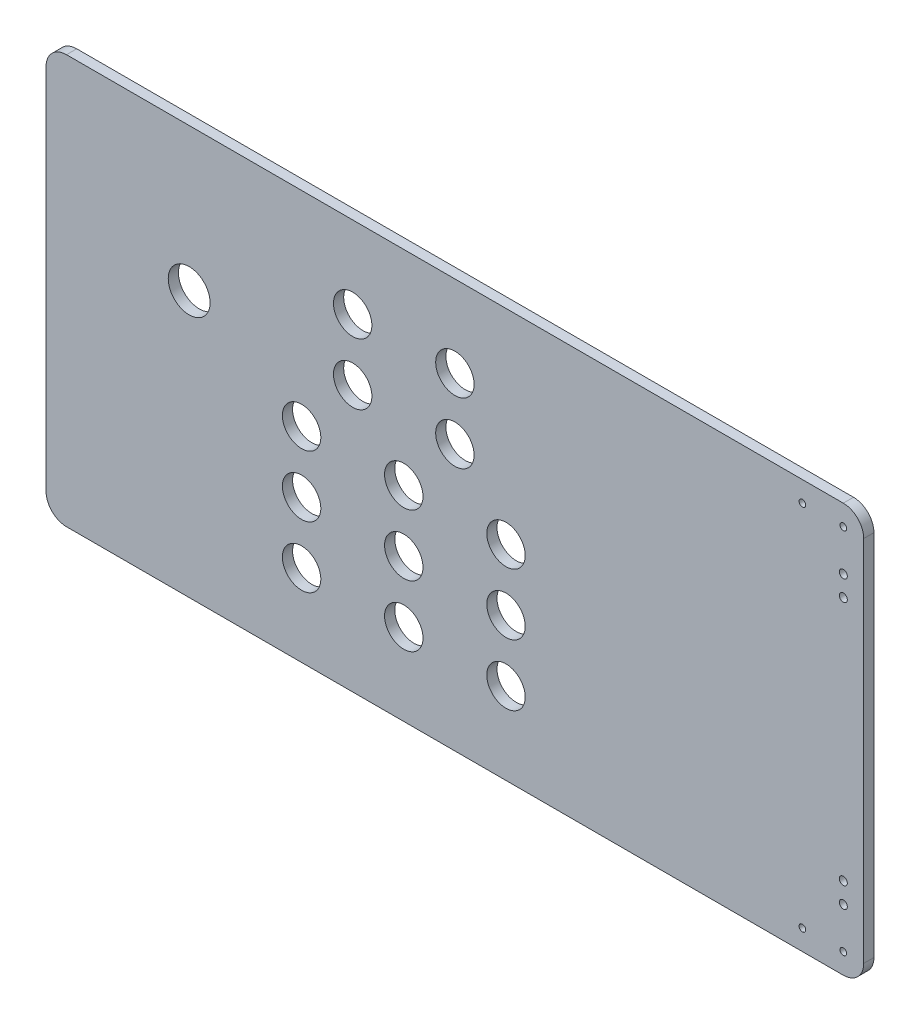
SolidWorks part; units mm, degrees
material "PC High Viscosity"
ref_plane "Front Plane" through (0, 0, 0) normal (0, 0, 1) x (1, 0, 0)
ref_plane "Top Plane" through (0, 0, 0) normal (0, 1, 0) x (1, 0, 0)
ref_plane "Right Plane" through (0, 0, 0) normal (1, 0, 0) x (0, 0, -1)
sketch "Sketch1" plane through (0, 0, 0) normal (0, 0, 1) x (1, 0, 0)
  line L1 (0, 0) -> (508, 0)
  line L2 (0, 0) -> (0, 254)
  line L3 (0, 254) -> (508, 254)
  line L4 (508, 0) -> (508, 254)
  dimension "D1" = 508
  dimension "D2" = 254
extrude "Boss-Extrude1" add sketch "Sketch1" along normal blind 6.35
sketch "Sketch3" plane through (0, 0, 0) normal (0, 0, -1) x (-1, 0, 0)
  line L0 (0, 0) -> (-508, 0) construction
  line L11 (-508, 254) -> (0, 254) construction
  line L17 (0, 254) -> (0, 0) construction
  line L18 (-508, 0) -> (-508, 254) construction
  line L19 (0, 254) -> (-25.4, 254) construction
  line L20 (0, 254) -> (0, 0) construction
  line L21 (0, 0) -> (-25.4, 0) construction
  line L22 (-25.4, 254) -> (-25.4, 0) construction
  line L23 (-508, 0) -> (-25.4, 0) construction
  line L24 (-508, 0) -> (-508, 25.4) construction
  line L25 (-508, 25.4) -> (-25.4, 25.4) construction
  line L26 (-25.4, 0) -> (-25.4, 25.4) construction
  line L27 (-508, 254) -> (-25.4, 254) construction
  line L28 (-508, 254) -> (-508, 228.6) construction
  line L29 (-508, 228.6) -> (-25.4, 228.6) construction
  line L30 (-25.4, 254) -> (-25.4, 228.6) construction
  circle A8 centre (-158.75, 88.9) radius 11.938
  circle A10 centre (-222.25, 88.9) radius 11.938
  circle A11 centre (-158.75, 50.8) radius 11.938
  circle A13 centre (-222.25, 50.8) radius 11.938
  circle A15 centre (-222.25, 127) radius 11.938
  circle A16 centre (-285.75, 127) radius 11.938
  circle A17 centre (-285.75, 88.9) radius 11.938
  circle A18 centre (-285.75, 50.8) radius 11.938
  circle A19 centre (-254, 203.2) radius 11.938
  circle A20 centre (-190.5, 203.2) radius 11.938
  circle A21 centre (-158.75, 127) radius 11.938
  circle A23 centre (-190.5, 165.1) radius 11.938
  circle A24 centre (-254, 165.1) radius 11.938
  circle A27 centre (-88.9, 165.1) radius 13
  circle A28 centre (-88.9, 165.1) radius 49.25 construction
  dimension "D2" = 23.876
  dimension "D3" = 63.5
  dimension "D4" = 38.1
  dimension "D5" = 38.1
  dimension "D6" = 63.5
  dimension "D7" = 25.4
  dimension "D8" = 38.1
  dimension "D9" = 38.1
  dimension "D10" = 25.4
  dimension "D11" = 23.876
  dimension "D12" = 63.5
  dimension "D13" = 26
  dimension "D14" = 98.5
  dimension "D15" = 31.75
  dimension "D16" = 50.8
  dimension "D17" = 25.4
  dimension "D18" = 88.9
  dimension "D19" = 88.9
  dimension "D20" = 254
extrude "Cut-Extrude2" cut sketch "Sketch3" against normal through all contours A18 | A17 | A16 | A24 | A10 | A8 | A23 | A11 | A13 | A15 | A21 | A27 | A20 | A19 region at (158.75, 88.9, 0) region at (222.25, 88.9, 0) region at (158.75, 50.8, 0) region at (222.25, 50.8, 0) region at (285.75, 127, 0) region at (285.75, 88.9, 0) region at (285.75, 50.8, 0) region at (190.5, 165.1, 0) region at (254, 165.1, 0)
fillet "Fillet1" radius 12.7 4 edges at (508, 0, 3.175) (0, 0, 3.175) (0, 254, 3.175) (508, 254, 3.175)
sketch "Sketch4" plane through (0, 0, 0) normal (0, 0, -1) x (-1, 0, 0)
  line L8 (-508, 12.7) -> (-508, 241.3) construction
  line L11 (-495.3, 254) -> (-12.7, 254) construction
  line L12 (-618.7392, 127) -> (68.6032, 127) construction
  circle A2 centre (-495.3205, 241.3) radius 2.0701
  circle A3 centre (-469.9205, 241.3) radius 2.0701
  circle A6 centre (-495.3205, 215.9) radius 2.4892
  circle A7 centre (-495.3205, 203.2) radius 2.4892
  circle A16 centre (-469.9205, 12.7) radius 2.0701
  circle A17 centre (-495.3205, 50.8) radius 2.4892
  circle A18 centre (-495.3205, 38.1) radius 2.4892
  circle A19 centre (-495.3205, 12.7) radius 2.0701
  dimension "D2" = 12.6795
  dimension "D8" = 127
  dimension "D5" = 4.9784
  dimension "D6" = 4.1402
  dimension "D7" = 12.7
  dimension "D3" = 38.1
  dimension "D4" = 50.8
  dimension "D13" = 25.4
extrude "Cut-Extrude3" cut sketch "Sketch4" against normal through all
